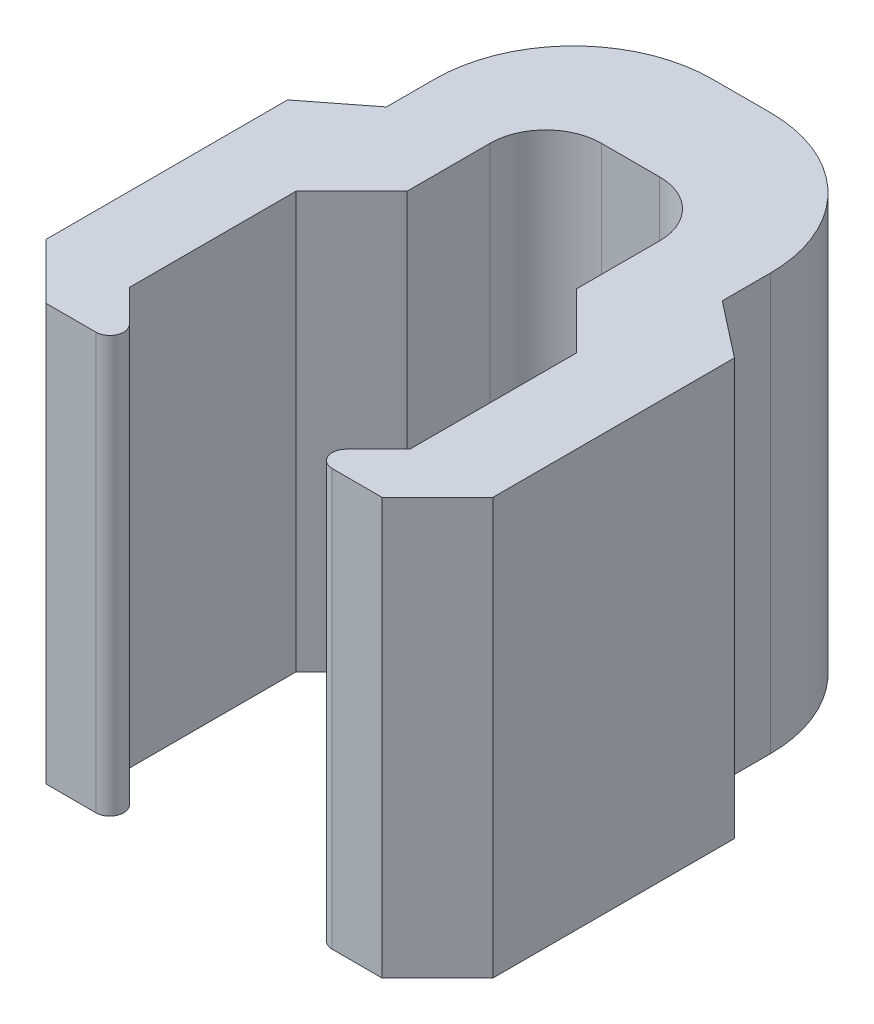
SolidWorks part; units mm, degrees
ref_plane "Front Plane" through (0, 0, 0) normal (0, 0, 1) x (1, 0, 0)
ref_plane "Top Plane" through (0, 0, 0) normal (0, 1, 0) x (1, 0, 0)
ref_plane "Right Plane" through (0, 0, 0) normal (1, 0, 0) x (0, 0, -1)
sketch "Sketch2" plane through (0, 0, 0) normal (0, 1, 0) x (1, 0, 0)
  line L0 (-11.1661, -0.629) -> (-14.1661, -0.629)
  line L1 (-11.1661, 14.371) -> (-1.0661, 14.371)
  line L2 (-11.1661, 14.371) -> (-11.1661, -0.629)
  line L3 (-11.1661, -0.629) -> (-1.0661, -0.629)
  line L4 (-1.0661, 14.371) -> (-1.0661, -0.629)
  line L5 (-14.1661, -0.629) -> (-14.1661, 18.371)
  line L6 (-14.1661, 18.371) -> (1.9339, 18.371)
  line L7 (1.9339, 18.371) -> (1.9339, -0.629)
  line L8 (1.9339, -0.629) -> (-1.0661, -0.629)
  line L9 (-11.1661, 1.371) -> (-9.1661, -0.629)
  line L10 (-1.0661, 1.371) -> (-3.0661, -0.629)
  line L11 (-11.1661, 7.371) -> (-9.1661, 9.371)
  line L12 (-9.1661, 9.371) -> (-9.1661, 14.371)
  line L13 (-3.0661, 9.371) -> (-1.0661, 7.371)
  line L14 (-3.0661, 9.371) -> (-3.0661, 14.371)
  line L15 (-14.1661, 10.071) -> (-12.1661, 11.6314)
  line L16 (-12.1661, 11.6314) -> (-12.1661, 18.371)
  line L17 (1.9339, 10.071) -> (-0.0661, 11.6314)
  line L18 (-0.0661, 11.6314) -> (-0.0661, 18.371)
  point P9 (-14.1661, 8.871)
  point P24 (0, 0)
  point P26 (0, 0)
  point P27 (0, 0)
  point P28 (-0.1736, 11.6314)
  dimension "D1" = 10.1
  dimension "D2" = 15
  dimension "D3" = 3
  dimension "D4" = 3
  dimension "D5" = 4
  dimension "D6" = 2
  dimension "D7" = 2
  dimension "D8" = 10
  dimension "D9" = 3
extrude "Boss-Extrude1" add sketch "Sketch2" along normal blind 15 contours L8 L7 L6 L5 L0 L2 L1 L4 | L11 L12 L1 L2 | L14 L13 L4 L1 | L4 L10 L3 | L9 L2 L3 region at (-12.6661, 0, 0.3799) region at (-10.4994, 0, -0.0377) region at (-10.2217, 0, -11.3433) region at (-1.7328, 0, -0.0377) region at (-2.0105, 0, -11.3433)
chamfer "Chamfer1" distance 2 angle 45 2 edges at (-14.1661, 7.5, 0.629) (1.9339, 7.5, 0.629)
fillet "Fillet1" radius 2 2 edges at (-3.0661, 7.5, -14.371) (-9.1661, 7.5, -14.371)
fillet "Fillet3" radius 5 2 edges at (-0.0661, 7.5, -18.371) (-12.1661, 7.5, -18.371)
fillet "Fillet4" radius 0.5 2 edges at (-3.0661, 7.5, 0.629) (-9.1661, 7.5, 0.629)
